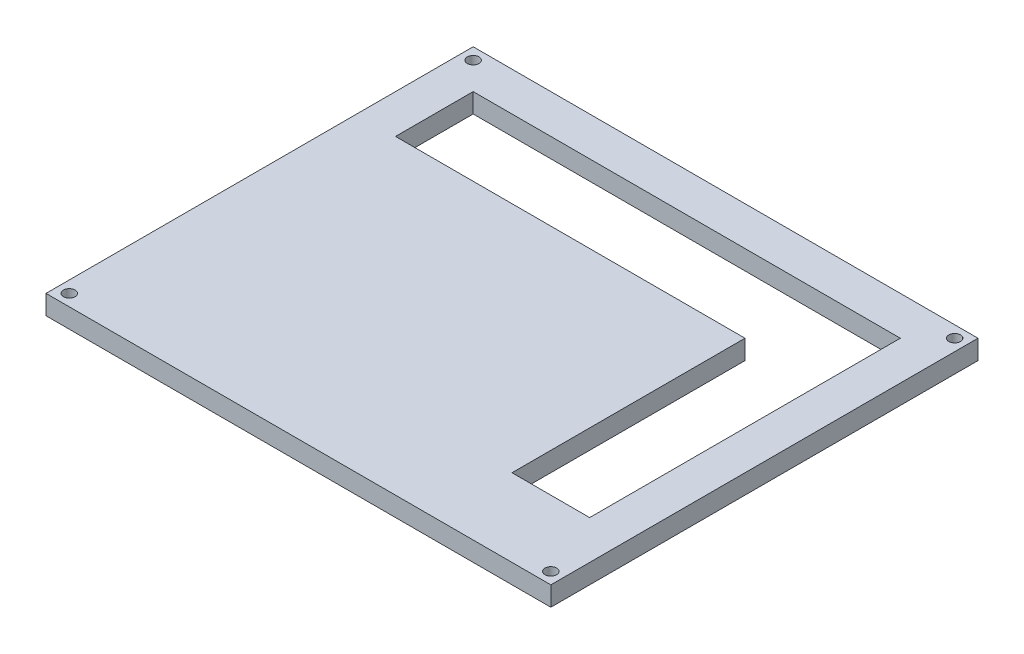
SolidWorks part; units mm, degrees
ref_plane "Front Plane" through (0, 0, 0) normal (0, 0, 1) x (1, 0, 0)
ref_plane "Top Plane" through (0, 0, 0) normal (0, 1, 0) x (1, 0, 0)
ref_plane "Right Plane" through (0, 0, 0) normal (1, 0, 0) x (0, 0, -1)
sketch "Sketch1" plane through (0, 0, 0) normal (0, 1, 0) x (1, 0, 0)
  line L1 (-65, 55) -> (65, 55)
  line L2 (-65, 55) -> (-65, -55)
  line L3 (-65, -55) -> (65, -55)
  line L4 (65, 55) -> (65, -55)
  line L5 (-65, 55) -> (65, -55) construction
  line L6 (-65, -55) -> (65, 55) construction
  point P0 (0, 0)
  dimension "D1" = 130
  dimension "D2" = 110
extrude "Boss-Extrude1" add sketch "Sketch1" along normal blind 5
sketch "Sketch2" plane through (0, 5, 0) normal (0, 1, 0) x (1, 0, 0)
  line L0 (-65, 55) -> (-65, -55) construction
  line L1 (65, 55) -> (-65, 55) construction
  circle A0 centre (-62, 52) radius 1.5
  dimension "D3" = 3
  dimension "D1" = 3
  dimension "D2" = 3
extrude "Cut-Extrude1" cut sketch "Sketch2" against normal through all
mirror "Mirror1" about plane through (0, 0, 0) normal (0, 0, 1) of "Cut-Extrude1"
mirror "Mirror2" about plane through (0, 0, 0) normal (1, 0, 0) of "Mirror1"
sketch "Sketch3" plane through (0, 5, 0) normal (0, 1, 0) x (1, 0, 0)
  line L0 (-55, 25) -> (35, 25)
  line L5 (-55, 45) -> (55, 45)
  line L6 (-55, 45) -> (-55, 25)
  line L8 (55, 45) -> (55, 25)
  line L9 (-55, 45) -> (55, 25) construction
  line L10 (-55, 25) -> (55, 45) construction
  line L11 (55, 25) -> (35, 25) construction
  line L12 (55, 25) -> (55, -35)
  line L13 (55, -35) -> (35, -35)
  line L14 (35, 25) -> (35, -35)
  point P0 (0, 35)
  dimension "D1" = 110
  dimension "D2" = 20
  dimension "D3" = 35
  dimension "D4" = 20
  dimension "D5" = 60
extrude "Cut-Extrude2" cut sketch "Sketch3" against normal through all
